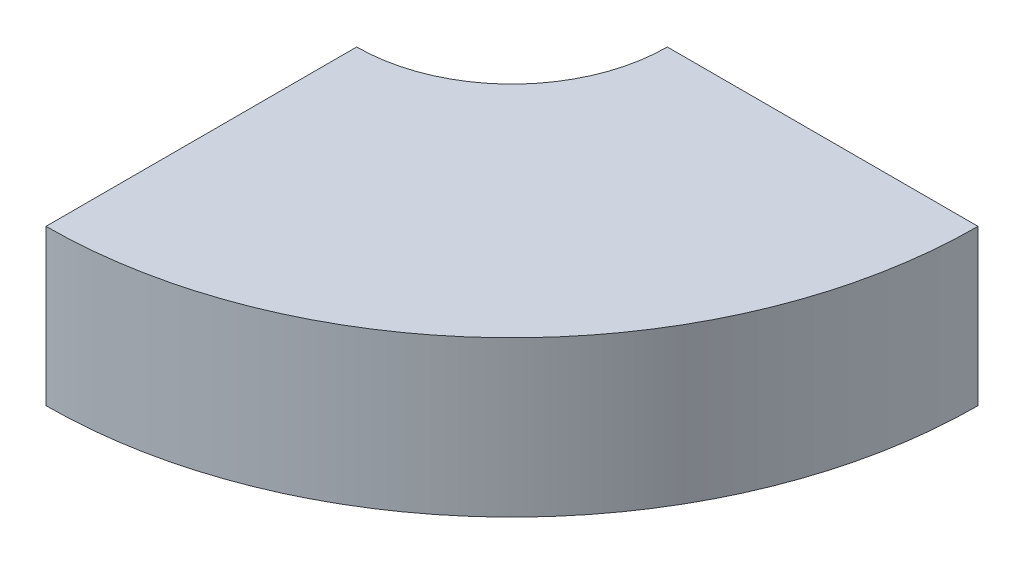
SolidWorks part; units mm, degrees
ref_plane "Front Plane" through (0, 0, 0) normal (0, 0, 1) x (1, 0, 0)
ref_plane "Top Plane" through (0, 0, 0) normal (0, 1, 0) x (1, 0, 0)
ref_plane "Right Plane" through (0, 0, 0) normal (1, 0, 0) x (0, 0, -1)
sketch "Sketch2" plane through (0, 0, 0) normal (0, 1, 0) x (1, 0, 0)
  line L0 (2, 0) -> (6, 0)
  line L1 (0, -2) -> (0, -6)
  arc A2 (0, -6) -> (6, 0) centre (0, 0) ccw
  arc A3 (0, -2) -> (2, 0) centre (0, 0) ccw
  dimension "D3" = 90
  dimension "D1" = 4
  dimension "D2" = 2
  dimension "D5" = 2
extrude "Boss-Extrude1" add sketch "Sketch2" along normal blind 2 contours L1 | L0 region at (2.7587, 0, 2.7587)
